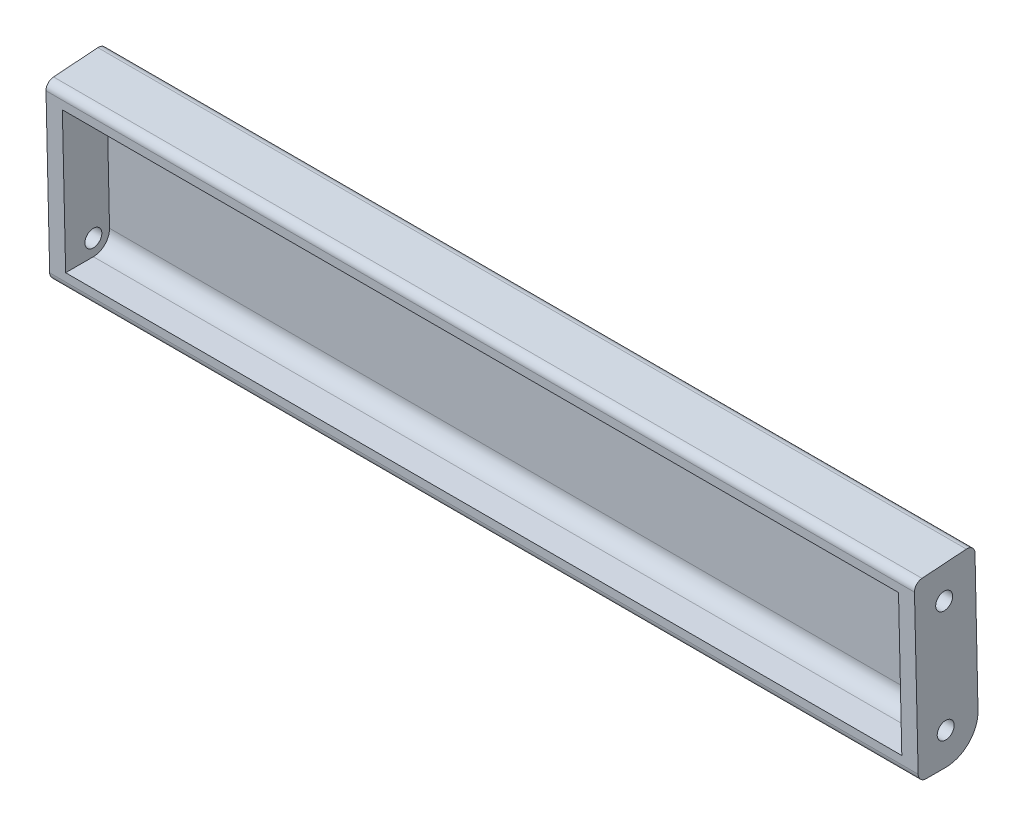
SolidWorks part; units mm, degrees
material "Perspex (TM) GS Acrylic Cast Sheet"
ref_plane "Front Plane" through (0, 0, 0) normal (0, 0, 1) x (1, 0, 0)
ref_plane "Top Plane" through (0, 0, 0) normal (0, 1, 0) x (1, 0, 0)
ref_plane "Right Plane" through (0, 0, 0) normal (1, 0, 0) x (0, 0, -1)
sketch "Sketch1" plane through (0, 0, 0) normal (1, 0, 0) x (0, 0, -1)
  line L11 (70.262, -14.8585) -> (65.4456, -14.8585)
  line L33 (64.3933, 28.6232) -> (75.3796, 29.4059)
  line L34 (62.5359, 26.5822) -> (63.4461, -12.9046)
  line L35 (77.5212, 27.4542) -> (78.2599, -6.6753)
  line L36 (70.262, -6.8585) -> (70.262, -14.8585) construction
  line L37 (69.8864, 29.0145) -> (69.8864, 21.0145) construction
  arc A6 (78.2599, -6.6753) -> (70.262, -14.8585) centre (70.262, -6.8585) cw
  circle A10 centre (70.262, -6.8585) radius 2.1 construction
  arc A17 (64.3933, 28.6232) -> (62.5359, 26.5822) centre (64.5354, 26.6283) ccw
  arc A18 (75.3796, 29.4059) -> (77.5212, 27.4542) centre (75.5217, 27.4109) cw
  circle A20 centre (69.8864, 21.0145) radius 2.1 construction
  arc A22 (65.4456, -14.8585) -> (63.4461, -12.9046) centre (65.4456, -12.8585) cw
  dimension "D2" = 2
  dimension "D4" = 8
  dimension "D1" = 2
extrude "Boss-Extrude1" add sketch "Sketch1" along normal blind 215
shell "Shell1" thickness 4 removed face at (107.5, 6.8388, -62.991)
sketch "Sketch3" plane through (215, 0, 0) normal (1, 0, 0) x (0, 0, -1)
  line L11 (70.262, -14.8585) -> (65.4456, -14.8585) construction
  line L33 (64.3933, 28.6232) -> (75.3796, 29.4059) construction
  line L34 (62.5359, 26.5822) -> (63.4461, -12.9046) construction
  line L35 (77.5212, 27.4542) -> (78.2599, -6.6753) construction
  line L36 (70.262, -6.8585) -> (70.262, -14.8585) construction
  line L37 (69.8864, 29.0145) -> (69.8864, 21.0145) construction
  arc A6 (78.2599, -6.6753) -> (70.262, -14.8585) centre (70.262, -6.8585) cw construction
  circle A10 centre (70.262, -6.8585) radius 2.1
  arc A17 (64.3933, 28.6232) -> (62.5359, 26.5822) centre (64.5354, 26.6283) ccw construction
  arc A18 (75.3796, 29.4059) -> (77.5212, 27.4542) centre (75.5217, 27.4109) cw construction
  circle A20 centre (69.8864, 21.0145) radius 2.1
  arc A22 (65.4456, -14.8585) -> (63.4461, -12.9046) centre (65.4456, -12.8585) cw construction
  point P13 (75.5217, 27.4109)
  dimension "D2" = 2
  dimension "D4" = 8
  dimension "D1" = 2
extrude "Cut-Extrude1" cut sketch "Sketch3" against normal through all
fillet "Fillet1" radius 2 1 edges at (107.5, 25.2666, -73.5676)
